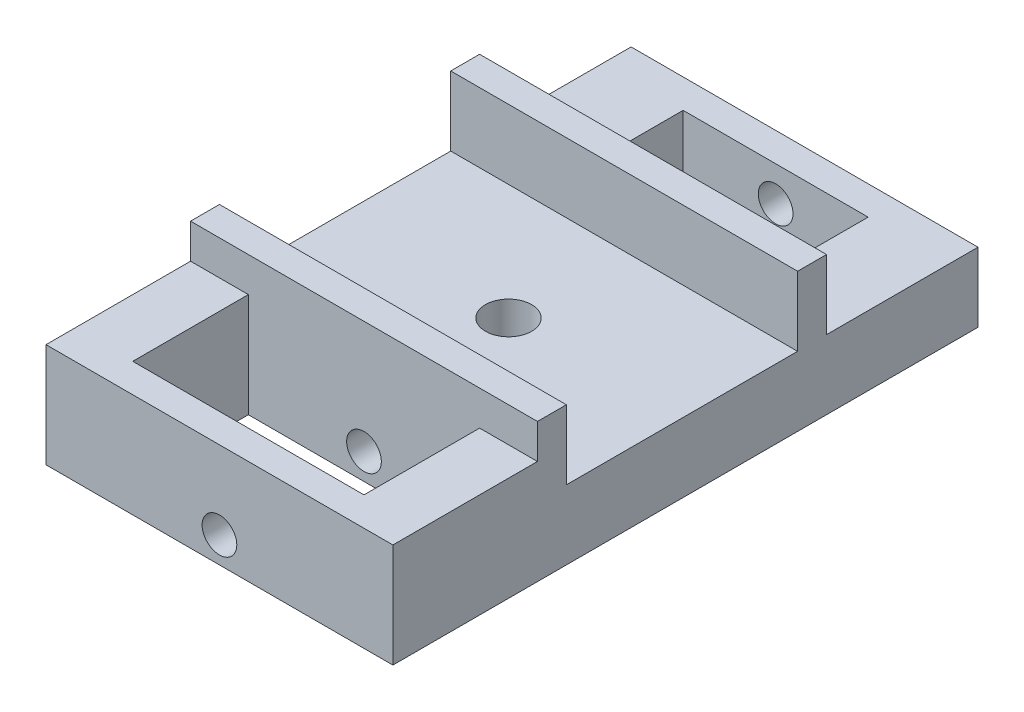
SolidWorks part; units mm, degrees
ref_plane "Front" through (0, 0, 0) normal (0, 0, 1) x (1, 0, 0)
ref_plane "Top" through (0, 0, 0) normal (0, 1, 0) x (1, 0, 0)
ref_plane "Right" through (0, 0, 0) normal (1, 0, 0) x (0, 0, -1)
sketch "Sketch1" plane through (0, 0, 0) normal (0, 1, 0) x (1, 0, 0)
  line L0 (0, -20) -> (0, -22.5)
  line L1 (0, 0) -> (-30, 0)
  line L2 (0, 0) -> (0, -20)
  line L3 (0, -20) -> (-30, -20)
  line L4 (-30, 0) -> (-30, -20)
  line L5 (0, -22.5) -> (-30, -22.5)
  line L6 (-30, -22.5) -> (-30, -20)
  line L7 (0, 0) -> (-7, 0)
  line L8 (-30, 0) -> (0, 0)
  line L9 (-30, 0) -> (-30, 2.5)
  line L10 (-30, 2.5) -> (0, 2.5)
  line L11 (0, 0) -> (0, 2.5)
  line L12 (-30, 0) -> (-23, 0)
  line L13 (-30, 2.5) -> (-30, 13.1)
  line L14 (-30, 13.1) -> (0, 13.1)
  line L15 (0, 13.1) -> (0, 2.5)
  line L16 (0, 13.1) -> (0, 15.6)
  line L17 (0, 15.6) -> (-30, 15.6)
  line L18 (-30, 15.6) -> (-30, 13.1)
  line L19 (-7, 0) -> (-7, 15.6)
  line L20 (-23, 0) -> (-23, 15.6)
  dimension "D1" = 20
  dimension "D2" = 2.5
  dimension "D3" = 2.5
  dimension "D4" = 30
  dimension "D5" = 7
  dimension "D6" = 7
  dimension "D7" = 10.6
  dimension "D8" = 2.5
extrude "Boss-Extrude1" add sketch "Sketch1" along normal blind 6 contours L1 L8 L4 L3 L2 | L6 L5 L0 L3 | L20 L1 L19 L10 | L19 L1 L11 L10 | L19 L10 L15 L14 | L19 L14 L16 L17 | L20 L14 L19 L17 | L14 L20 L17 L18 | L10 L20 L14 L13 | L8 L20 L10 L9 region at (-15, 0, 10) region at (-15, 0, 21.25) region at (-3.5, 0, -1.25) region at (-15, 0, -1.25) region at (-3.5, 0, -7.8) region at (-26.5, 0, -1.25) region at (-3.5, 0, -14.35) region at (-26.5, 0, -7.8) region at (-15, 0, -14.35) region at (-26.5, 0, -14.35)
extrude "Boss-Extrude2" add sketch "Sketch1<3>" along normal blind 12 contours L19 L1 L11 L10 | L20 L1 L19 L10 | L6 L5 L0 L3 | L8 L20 L10 L9 region at (-15, 0, 21.25) region at (-3.5, 0, -1.25) region at (-15, 0, -1.25) region at (-26.5, 0, -1.25)
sketch "Sketch1<3>" plane through (0, 0, 0) normal (0, 1, 0) x (1, 0, 0) same geometry as "Sketch1"
sketch "Sketch3" plane through (0, 0, -15.6) normal (0, 0, -1) x (-1, 0, 0)
  line L0 (30, 3) -> (23, 3)
  line L1 (30, 6) -> (30, 0) construction
  line L2 (23, 3) -> (15, 3)
  circle A0 centre (15, 3) radius 1.5
  dimension "D1" = 7
  dimension "D2" = 8
extrude "Cut-Extrude2" cut sketch "Sketch3" against normal blind 16 contours A0
ref_plane "Plane1" through (0, 0, 10) normal (0, 0, -1) x (-1, 0, 0)
sketch "Sketch2" plane through (0, 6, 0) normal (0, 1, 0) x (1, 0, 0)
  line L0 (-30, -10) -> (0, -10)
  line L1 (-30, 0) -> (-30, -20) construction
  line L2 (0, 0) -> (0, -20) construction
  circle A0 centre (-15, -10) radius 2
extrude "Cut-Extrude1" cut sketch "Sketch2" against normal through all contours L0 A0 | L0 A0 region at (-15, 6, 9.1512) region at (-15, 6, 10.8488)
sketch "Sketch5" plane through (0, 0, 0) normal (0, -1, 0) x (1, 0, 0)
  line L0 (-30, 22.5) -> (-25, 22.5)
  line L1 (-30, 22.5) -> (0, 22.5)
  line L2 (-30, 22.5) -> (-30, 32.5)
  line L3 (0, 22.5) -> (0, 32.5)
  line L4 (-30, 32.5) -> (0, 32.5)
  line L5 (-25, 22.5) -> (-25, 32.5)
  line L6 (-25, 32.5) -> (-5, 32.5)
  line L7 (-5, 32.5) -> (-5, 22.5)
  line L8 (-5, 22.5) -> (0, 22.5)
  line L9 (-30, 32.5) -> (-30, 35)
  line L10 (-30, 35) -> (0, 35)
  line L11 (0, 35) -> (0, 32.5)
  line M7 (0, 22.5) -> (-30, 22.5)
  dimension "D1" = 10
  dimension "D2" = 5
  dimension "D3" = 5
  dimension "D4" = 2.5
extrude "Boss-Extrude3" add sketch "Sketch5" against normal blind 9 contours L5 L4 L2 M7 | L11 L10 L9 L4 | L4 L7 L3 M7 region at (-27.5, 0, 27.5) region at (-15, 0, 33.75) region at (-2.5, 0, 27.5)
sketch "Sketch6" plane through (0, 0, 35) normal (0, 0, 1) x (1, 0, 0)
  line L0 (0, 0) -> (0, 4.5)
  line L1 (0, 9) -> (0, 0) construction
  line L2 (0, 4.5) -> (0, 2.25)
  line L3 (0, 2.25) -> (-15, 2.25)
  circle A1 centre (-15, 2.25) radius 1.5
extrude "Cut-Extrude4" cut sketch "Sketch6" against normal blind 20 contours A1 region at (-16.4576, 2.25, 35)
